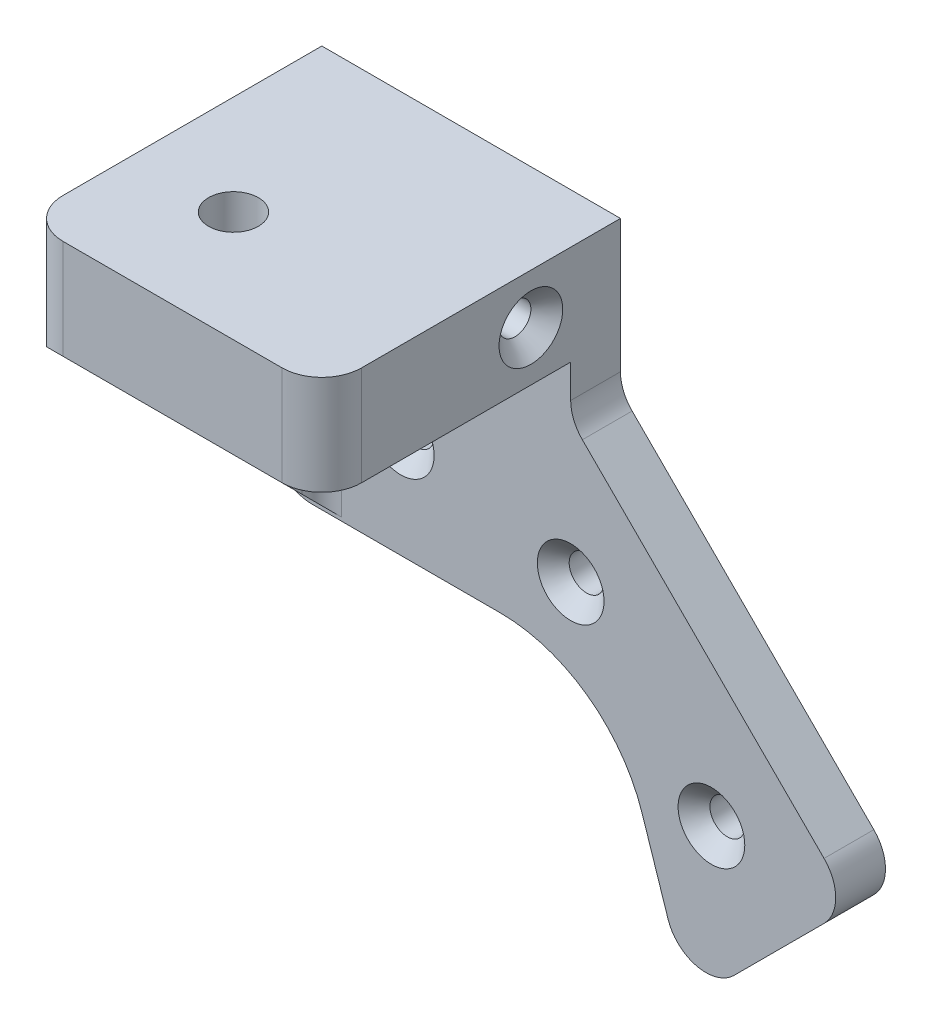
SolidWorks part; units mm, degrees
ref_plane "Front Plane" through (0, 0, 0) normal (0, 0, 1) x (1, 0, 0)
ref_plane "Top Plane" through (0, 0, 0) normal (0, 1, 0) x (1, 0, 0)
ref_plane "Right Plane" through (0, 0, 0) normal (1, 0, 0) x (0, 0, -1)
sketch "Sketch1" plane through (0, 0, 0) normal (0, 0, 1) x (1, 0, 0)
  line L0 (15, 27.5) -> (15, 12.5)
  line L5 (-15, 27.5) -> (15, 27.5)
  line L6 (-15, 27.5) -> (-15, -27.5)
  line L7 (-15, -27.5) -> (15, -27.5)
  line L9 (15, 12.5) -> (43.2843, -15.7843)
  line L10 (-15, -27.5) -> (15, 27.5) construction
  line L11 (43.2843, -15.7843) -> (23.2843, -35.7843)
  line L12 (23.2843, -35.7843) -> (15, -27.5)
  point P0 (0, 0)
  dimension "D1" = 45
  dimension "D2" = 55
  dimension "D3" = 30
  dimension "D4" = 40
  dimension "D5" = 15
extrude "Boss-Extrude1" add sketch "Sketch1" along normal blind 5
sketch "Sketch3" plane through (0, 0, 5) normal (0, 0, 1) x (1, 0, 0)
  line L0 (15, 12.5) -> (15, 27.5) construction
  line L1 (-15, 27.5) -> (15, 27.5)
  line L2 (-15, 27.5) -> (-15, 17.5)
  line L3 (-15, 17.5) -> (15, 17.5)
  line L4 (15, 27.5) -> (15, 17.5)
  dimension "D1" = 10
extrude "Boss-Extrude2" add sketch "Sketch3" along normal blind 25
sketch "Sketch4" plane through (0, 27.5, 0) normal (0, 1, 0) x (1, 0, 0)
  line L0 (-15, -30) -> (-15, 0) construction
  line L1 (15, -30) -> (-15, -30) construction
  line L2 (15, -30) -> (15, -5) construction
  line L3 (15, -5) -> (-15, -5) construction
  line L4 (-15, -30) -> (-15, -5) construction
  line L5 (15, -30) -> (15, 0) construction
  line L6 (-15, 0) -> (15, 0) construction
  line L7 (-15, 0) -> (-15, 5) construction
  line L8 (-15, 5) -> (15, 5) construction
  line L9 (15, 0) -> (15, 5) construction
  circle A0 centre (-5, -18.88) radius 2.5
  circle A1 centre (-5, -18.88) radius 6.5 construction
  dimension "D3" = 13
  dimension "D4" = 5
  dimension "D1" = 25
  dimension "D2" = 5
  dimension "D5" = 23.88
  dimension "D6" = 20
extrude "Cut-Extrude1" cut sketch "Sketch4" against normal through all
sketch "Sketch6" plane through (-15, 0, 0) normal (-1, 0, 0) x (0, 0, 1)
  line L0 (30, 17.5) -> (5, -7.5)
  line L1 (5, 17.5) -> (5, -27.5) construction
  dimension "D1" = 45
rib "Rib1" sketch "Sketch6" sketch "Sketch6" thickness 5 extrusion direction parallel to sketch draft on no parameters "D1"=5
sketch "Sketch7" plane through (0, 0, 5) normal (0, 0, 1) x (1, 0, 0)
  line L0 (22.1747, -18.1589) -> (26.8198, -32.2487)
  line L1 (-15, -7.8553) -> (7.9289, -7.8553)
  line L2 (-15, -7.8553) -> (-15, -27.5)
  line L3 (-15, -7.5) -> (-15, -27.5) construction
  line L4 (-15, -27.5) -> (15, -27.5) construction
  line L5 (15, 27.5) -> (-15, 27.5) construction
  line L6 (23.2843, -35.7843) -> (43.2843, -15.7843) construction
  line L7 (-15, -27.5) -> (23.2843, -35.7843)
  line L8 (23.2843, -35.7843) -> (26.8198, -32.2487)
  arc A0 (22.1747, -18.1589) -> (7.9289, -7.8553) centre (7.9289, -22.8553) ccw
  circle A1 centre (7.9289, -22.8553) radius 14 construction
  dimension "D1" = 1
  dimension "D2" = 5
extrude "Cut-Extrude2" cut sketch "Sketch7" against normal up to vertex (5 mm away) up to point (-15, -27.5, 0)
sketch "Sketch8" plane through (0, 17.5, 0) normal (0, -1, 0) x (-1, 0, 0)
  line L1 (0.2657, -18.88) -> (2.6329, -22.98)
  line L2 (2.6329, -22.98) -> (7.3671, -22.98)
  line L3 (7.3671, -22.98) -> (9.7343, -18.88)
  line L4 (9.7343, -18.88) -> (7.3671, -14.78)
  line L5 (7.3671, -14.78) -> (2.6329, -14.78)
  line L6 (2.6329, -14.78) -> (0.2657, -18.88)
  circle A0 centre (5, -18.88) radius 4.1 construction
  dimension "D1" = 8.2
extrude "Cut-Extrude3" cut sketch "Sketch8" against normal blind 5
fillet "Fillet1" radius 4 2 edges at (-15, 22.5, 30) (15, 22.5, 30)
sketch "Sketch9" plane through (0, 0, 5) normal (0, 0, 1) x (1, 0, 0)
  line L0 (15, -1.6421) -> (22.0711, 5.4289) construction
  line L1 (43.2843, -15.7843) -> (15, 12.5) construction
  line L2 (29.1421, -15.7843) -> (36.2132, -8.7132) construction
  line L3 (26.8198, -32.2487) -> (43.2843, -15.7843) construction
  line L4 (15, 12.5) -> (-5.3553, -7.8553) construction
  line L5 (7.9289, -7.8553) -> (-15, -7.8553) construction
  line L6 (15, 12.5) -> (-15, 12.5) construction
  line L7 (-15, 13.5) -> (-15, -7.5) construction
  circle A0 centre (15, -1.6421) radius 1.75
  circle A1 centre (29.1421, -15.7843) radius 1.75
  circle A2 centre (-2.0711, 2.5) radius 1.75
  dimension "D1" = 3.5
  dimension "D5" = 5
  dimension "D2" = 10
  dimension "D3" = 10
  dimension "D4" = 20
  dimension "D6" = 10
extrude "Cut-Extrude4" cut sketch "Sketch9" against normal through all
chamfer "Chamfer1" distance 1.6 angle 45 3 edges at (30.8921, -15.7843, 5) (16.75, -1.6421, 5) (-0.3211, 2.5, 5)
fillet "Fillet2" radius 4 4 edges at (15, 12.5, 2.5) (43.2843, -15.7843, 2.5) (26.8198, -32.2487, 2.5) (-15, -7.8553, 2.5)
sketch "Sketch10" plane through (15, 0, 0) normal (1, 0, 0) x (0, 0, -1)
  line L0 (-9, 17.5) -> (-9, 27.5) construction
  line L1 (-26, 17.5) -> (-5, 17.5) construction
  line L2 (-26, 27.5) -> (0, 27.5) construction
  line L3 (0, 14.1569) -> (0, 27.5) construction
  circle A0 centre (-9, 22.5) radius 1.6
  dimension "D1" = 3.2
  dimension "D2" = 9
extrude "Cut-Extrude5" cut sketch "Sketch10" against normal through all
sketch "Sketch11" plane through (-15, 0, 0) normal (-1, 0, 0) x (0, 0, 1)
  line L1 (10.5877, 19.75) -> (12.1754, 22.5)
  line L2 (12.1754, 22.5) -> (10.5877, 25.25)
  line L3 (10.5877, 25.25) -> (7.4123, 25.25)
  line L4 (7.4123, 25.25) -> (5.8246, 22.5)
  line L5 (5.8246, 22.5) -> (7.4123, 19.75)
  line L6 (7.4123, 19.75) -> (10.5877, 19.75)
  circle A0 centre (9, 22.5) radius 2.75 construction
  dimension "D1" = 5.5
extrude "Cut-Extrude6" cut sketch "Sketch11" against normal blind 4
chamfer "Chamfer2" distance 1.6 angle 45 1 edges at (15, 24.1, 9)
fillet "Fillet3" radius 2 1 edges at (-10, 5, 5)
